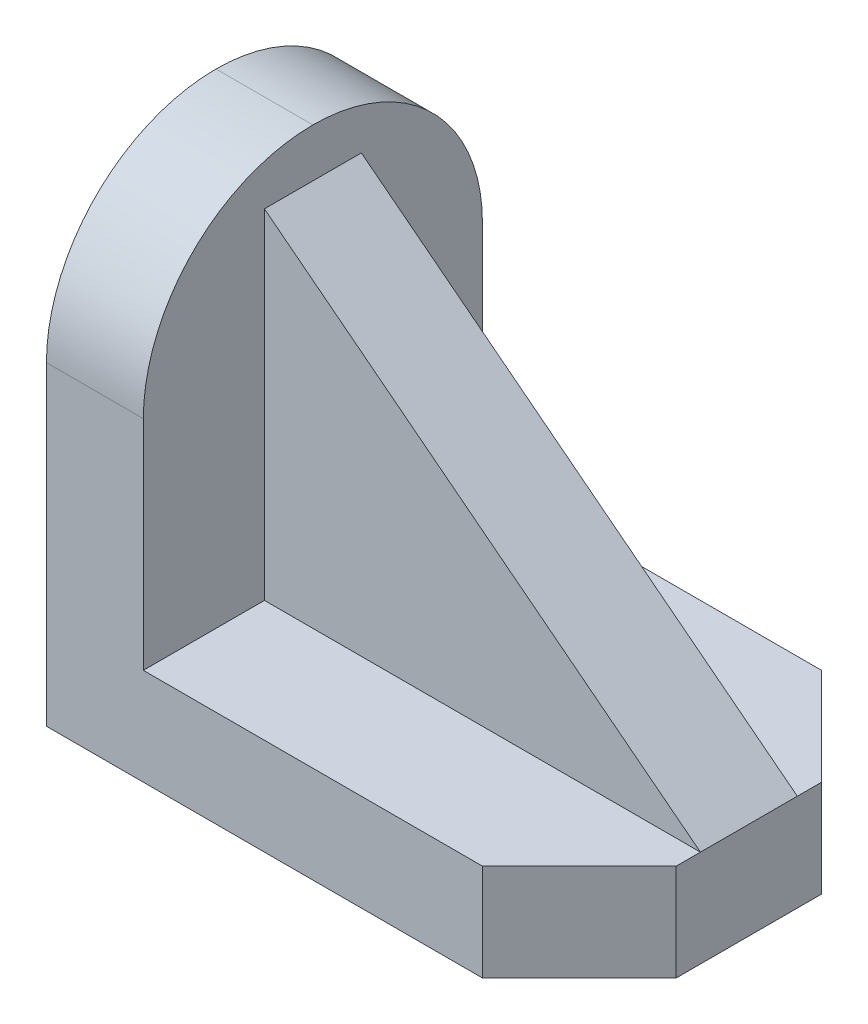
SolidWorks part; units mm, degrees
ref_plane "Front Plane" through (0, 0, 0) normal (0, 0, 1) x (1, 0, 0)
ref_plane "Top Plane" through (0, 0, 0) normal (0, 1, 0) x (1, 0, 0)
ref_plane "Right Plane" through (0, 0, 0) normal (1, 0, 0) x (0, 0, -1)
sketch "Sketch2" plane through (0, 0, 0) normal (0, 1, 0) x (1, 0, 0)
  line L1 (-33, 21) -> (33, 21)
  line L2 (-33, 21) -> (-33, -21)
  line L3 (-33, -21) -> (33, -21)
  line L4 (33, 21) -> (33, -21)
  line L5 (-33, 21) -> (33, -21) construction
  line L6 (-33, -21) -> (33, 21) construction
  point P0 (0, 0)
  dimension "D1" = 66
  dimension "D2" = 42
extrude "Boss-Extrude2" add sketch "Sketch2" along normal blind 12
chamfer "Chamfer1" distance 12 angle 45 2 edges at (33, 6, -21) (33, 6, 21)
sketch "Sketch4" plane through (0, 12, 0) normal (0, 1, 0) x (1, 0, 0)
  line L0 (21, 21) -> (-33, 21) construction
  line L1 (-33, -21) -> (-21, -21)
  line L2 (-33, -21) -> (-33, 21)
  line L3 (-33, 21) -> (-21, 21)
  line L4 (-21, -21) -> (-21, 21)
  dimension "D1" = 12
extrude "Boss-Extrude4" add sketch "Sketch4" along normal blind 48
fillet "Fillet2" radius 21 2 edges at (-27, 60, -21) (-27, 60, 21)
sketch "Sketch7" plane through (0, 0, 21) normal (0, 0, 1) x (1, 0, 0)
  line L0 (-21, 12) -> (33, 12)
  line L2 (33, 12) -> (-21, 54)
  line L4 (-21, 54) -> (-21, 12)
  dimension "D1" = 42
  dimension "D2" = 68.4105
extrude "Boss-Extrude5" add sketch "Sketch7" against normal blind 27
extrude "Cut-Extrude1" cut sketch "Sketch7<2>" against normal blind 15
sketch "Sketch7<2>" plane through (0, 0, 21) normal (0, 0, 1) x (1, 0, 0) same geometry as "Sketch7"
